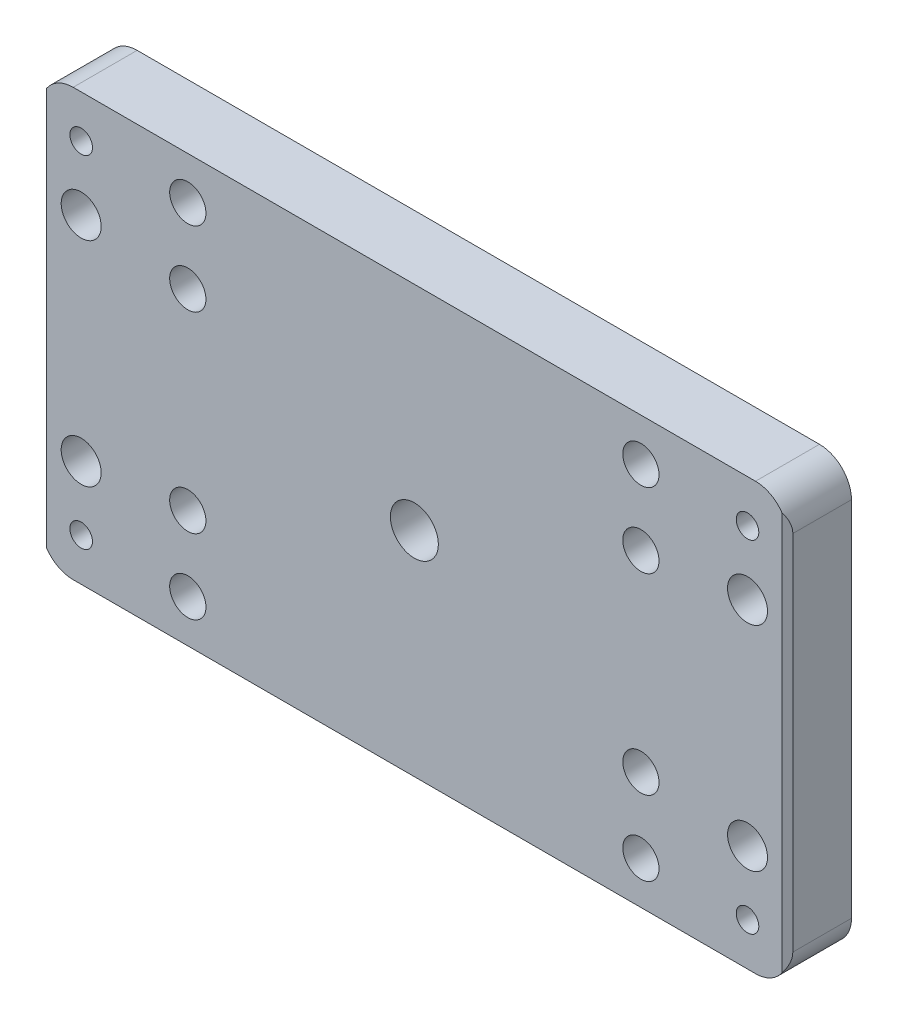
SolidWorks part; units mm, degrees
ref_plane "Front Plane" through (0, 0, 0) normal (0, 0, 1) x (1, 0, 0)
ref_plane "Top Plane" through (0, 0, 0) normal (0, 1, 0) x (1, 0, 0)
ref_plane "Right Plane" through (0, 0, 0) normal (1, 0, 0) x (0, 0, -1)
sketch "Sketch1" plane through (0, 0, 0) normal (0, 0, 1) x (1, 0, 0)
  line L9 (-70, -40) -> (70, -40)
  line L10 (-70, -40) -> (-70, 40)
  line L11 (-70, 40) -> (70, 40)
  line L12 (70, -40) -> (70, 40)
  line L13 (0, 40) -> (0, -40) construction
  line L14 (-70, 0) -> (70, 0) construction
  circle A0 centre (-62.5, 32) radius 2.117
  circle A1 centre (-62.5, 20.0002) radius 3.75
  circle A2 centre (-62.5, -32) radius 2.117
  circle A3 centre (-62.5, -19.9998) radius 3.75
  circle A4 centre (0, 0) radius 4.5
  circle A5 centre (62.5, 32) radius 2.117
  circle A6 centre (62.5, 20.0002) radius 3.75
  circle A7 centre (62.5, -19.9998) radius 3.75
  circle A8 centre (62.5, -32) radius 2.117
  dimension "D2" = 80
  dimension "D3" = 140
extrude "Boss-Extrude1" add sketch "Sketch1" along normal blind 12
sketch "Sketch2" plane through (0, 0, 12) normal (0, 0, 1) x (1, 0, 0)
  circle A0 centre (42.5, 32) radius 3.4
  circle A1 centre (-42.5, 32) radius 3.4
  circle A2 centre (-42.5, 18) radius 3.4
  circle A3 centre (42.5, 18) radius 3.4
  circle A4 centre (42.5, -18) radius 3.4
  circle A5 centre (42.5, -32) radius 3.4
  circle A6 centre (-42.5, -32) radius 3.4
  circle A7 centre (-42.5, -18) radius 3.4
extrude "Cut-Extrude1" cut sketch "Sketch2" against normal through all
fillet "Fillet1" radius 6 4 edges at (70, -40, 6) (70, 40, 6) (-70, 40, 6) (-70, -40, 6)
chamfer "Chamfer1" distance 1 angle 45 2 edges at (70, 0, 12) (-70, 0, 12) tangent propagation no
